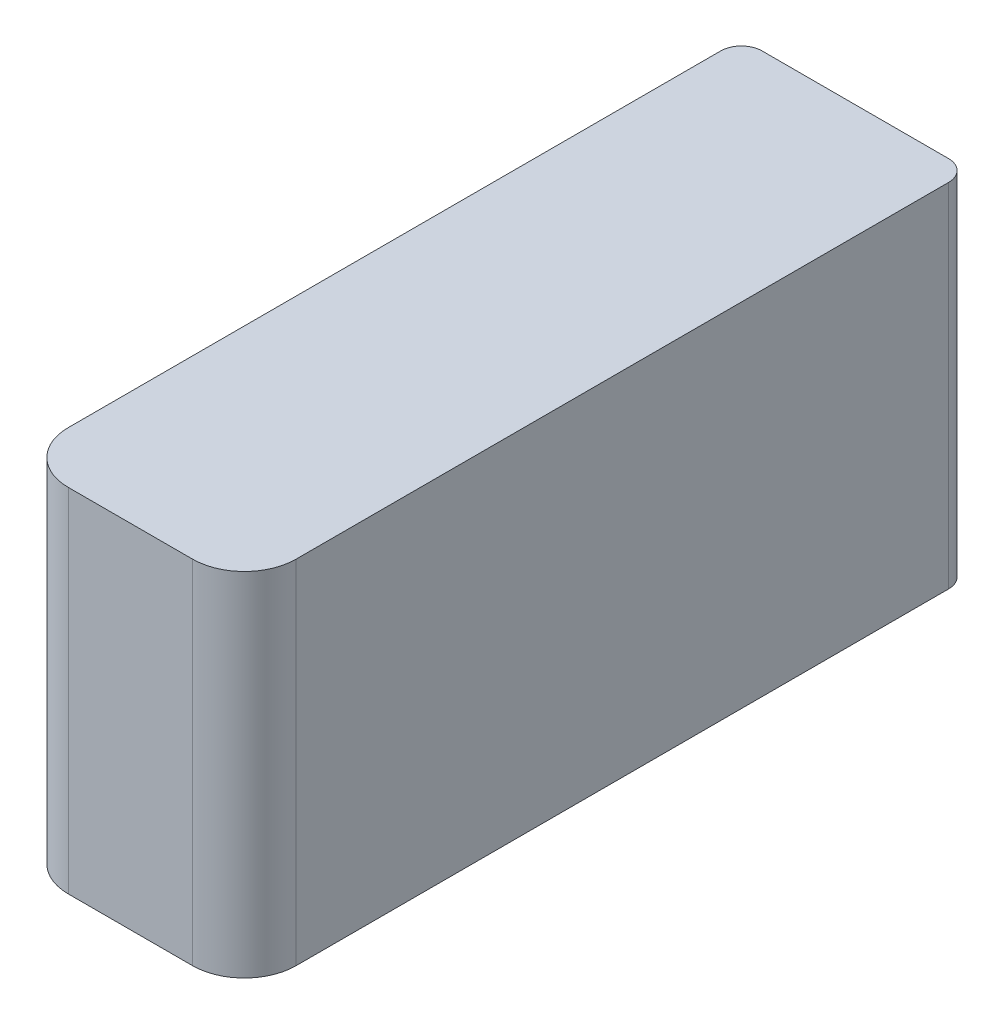
SolidWorks part; units mm, degrees
material "Batery"
ref_plane "Plano frontal" through (0, 0, 0) normal (0, 0, 1) x (1, 0, 0)
ref_plane "Plano superior" through (0, 0, 0) normal (0, 1, 0) x (1, 0, 0)
ref_plane "Plano direito" through (0, 0, 0) normal (1, 0, 0) x (0, 0, -1)
sketch "Sketch1" plane through (0, 0, 0) normal (0, 0, 1) x (1, 0, 0)
  line L1 (-11, -17) -> (11, -17)
  line L2 (-11, -17) -> (-11, 17)
  line L3 (-11, 17) -> (11, 17)
  line L4 (11, -17) -> (11, 17)
  line L5 (-11, -17) -> (11, 17) construction
  line L6 (-11, 17) -> (11, -17) construction
  point P0 (0, 0)
  dimension "D1" = 22
  dimension "D2" = 34
extrude "Boss-Extrude1" add sketch "Sketch1" along normal mid plane 70
fillet "Fillet1" radius 2 2 edges at (-11, 0, -35) (11, 0, -35)
fillet "Fillet2" radius 5 2 edges at (-11, 0, 35) (11, 0, 35)
